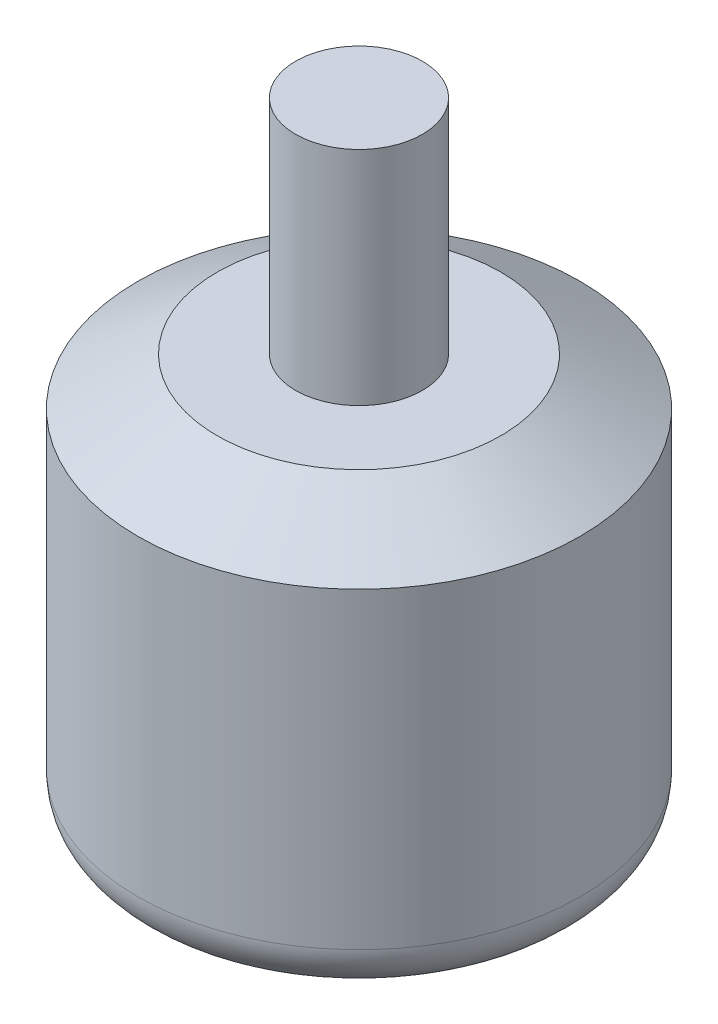
SolidWorks part; units mm, degrees
material "Copper"
ref_plane "Front Plane" through (0, 0, 0) normal (0, 0, 1) x (1, 0, 0)
ref_plane "Top Plane" through (0, 0, 0) normal (0, 1, 0) x (1, 0, 0)
ref_plane "Right Plane" through (0, 0, 0) normal (1, 0, 0) x (0, 0, -1)
sketch "Sketch1" plane through (0, 0, 0) normal (0, 1, 0) x (1, 0, 0)
  circle A0 centre (0, 0) radius 13.95
  dimension "D1" = 27.9
extrude "Boss-Extrude1" add sketch "Sketch1" along normal blind 25.7
chamfer "Chamfer1" distance 3 distance2 5 1 edges at (0, 25.7, 13.95) first distance on face at (0, 25.7, 13.95)
sketch "Sketch2" plane through (0, 25.7, 0) normal (0, 1, 0) x (1, 0, 0)
  circle A0 centre (0, 0) radius 4
extrude "Boss-Extrude2" add sketch "Sketch2" along normal blind 14
hole_wizard "M3x0.5 Tapped Hole1" positions "Sketch4" profile "Sketch3" tap size "M3x0.5" standard "ANSI Metric"
sketch "Sketch4" plane through (0, 0, 0) normal (0, -1, 0) x (-1, 0, 0)
  line L0 (0, 8) -> (0, -8) construction
  line L1 (-9.5, 0) -> (9.5, 0) construction
  point P6 (0, 8)
  point P7 (0, -8)
  point P9 (-9.5, 0)
  point P10 (9.5, 0)
  point P24 (0, 0)
  point P25 (0, 0)
  dimension "D1" = 16
  dimension "D2" = 19
sketch "Sketch3" plane through (0, 0, -8) normal (1, 0, 0) x (0, 0, -1)
  line L0 (0, 0) -> (0, 8.2511)
  line L1 (0, 8.2511) -> (1.25, 7.5)
  line L2 (1.25, 7.5) -> (1.25, 0)
  line L5 (1.25, 0) -> (0, 0)
  line L10 (0, 8.2511) -> (-1.25, 7.5) construction
  line L11 (0, -6.35) -> (0, 107.95) construction
  dimension "Tap Drill Dia." = 2.5
  dimension "Tap Drill Depth" = 7.5
  dimension "Drill Angle" = 118
cosmetic thread "Hole Thread1" parameters "D1"=6, "D2"=3
cosmetic thread "Hole Thread2" parameters "D1"=6, "D2"=3
cosmetic thread "Hole Thread3" parameters "D1"=6, "D2"=3
cosmetic thread "Hole Thread4" parameters "D1"=6, "D2"=3
fillet "Fillet1" radius 3 1 edges at (0, 0, 13.95)
sketch "Sketch5" plane through (0, 0, 0) normal (0, -1, 0) x (1, 0, 0)
  circle A0 centre (0, 0) radius 3
extrude "Boss-Extrude3" add sketch "Sketch5" along normal blind 2.5
sketch "Sketch6" plane through (0, 39.7, 0) normal (0, 1, 0) x (1, 0, 0)
  circle A0 centre (0, 0) radius 127
  dimension "D1" = 254
